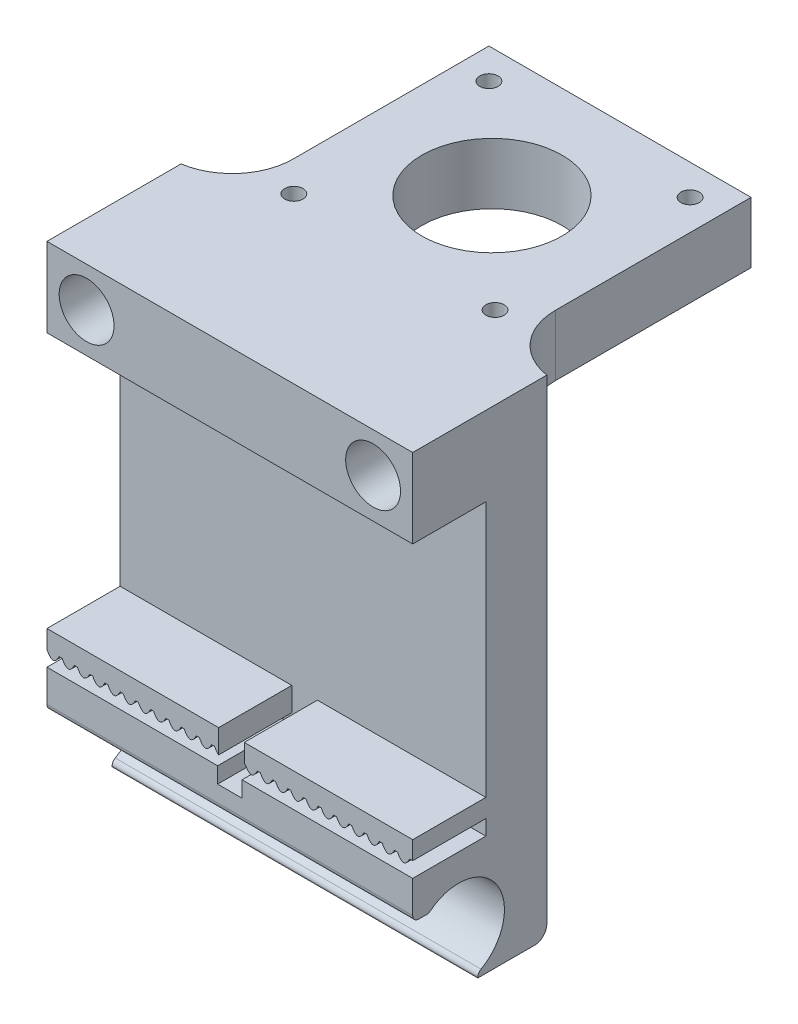
SolidWorks part; units mm, degrees
ref_plane "정면" through (0, 0, 0) normal (0, 0, 1) x (1, 0, 0)
ref_plane "윗면" through (0, 0, 0) normal (0, 1, 0) x (1, 0, 0)
ref_plane "우측면" through (0, 0, 0) normal (1, 0, 0) x (0, 0, -1)
sketch "스케치1" plane through (0, 0, 0) normal (0, 0, 1) x (1, 0, 0)
  line L1 (0, 0) -> (-60, 0)
  line L2 (0, 0) -> (0, 80)
  line L3 (0, 80) -> (-60, 80)
  line L4 (-60, 0) -> (-60, 80)
  dimension "D1" = 60
  dimension "D2" = 80
extrude "보스-돌출1" add sketch "스케치1" along normal blind 10
sketch "스케치2" plane through (0, 0, 10) normal (0, 0, 1) x (1, 0, 0)
  line L0 (0, 0) -> (0, 80) construction
  line L1 (-60, 80) -> (0, 80)
  line L2 (-60, 80) -> (-60, 67)
  line L3 (-60, 67) -> (0, 67)
  line L4 (0, 80) -> (0, 67)
  circle A0 centre (-6.5, 73.5) radius 4
  circle A1 centre (-53.5, 73.5) radius 4
  dimension "D2" = 6.5
  dimension "D3" = 6.5
  dimension "D4" = 6.5
  dimension "D1" = 13
extrude "보스-돌출2" add sketch "스케치2" along normal blind 12
sketch "스케치3" plane through (0, 0, 10) normal (0, 0, 1) x (1, 0, 0)
  line L0 (0, 0) -> (0, 67) construction
  line L1 (-60, 0) -> (0, 0)
  line L2 (-60, 0) -> (-60, 20)
  line L3 (-60, 20) -> (0, 20)
  line L4 (0, 0) -> (0, 20)
  dimension "D1" = 20
extrude "보스-돌출3" add sketch "스케치3" along normal blind 12
sketch "스케치6" plane through (0, 0, 0) normal (1, 0, 0) x (0, 0, -1)
  circle A0 centre (-14.4537, 7.5501) radius 7.5
extrude "컷-돌출1" cut sketch "스케치6" against normal blind 60
sketch "스케치7" plane through (0, 0, 0) normal (1, 0, 0) x (0, 0, -1)
  line L0 (-22, 7.7525) -> (-22, 0)
  line L1 (-22, 0) -> (-22, 20) construction
sketch "스케치8" plane through (0, 0, 0) normal (1, 0, 0) x (0, 0, -1)
  line L0 (-14.2542, 0) -> (-22, 0)
  line L1 (-22, 0) -> (0, 0) construction
  line L2 (-22, 0) -> (-22, 7.7525)
  line L3 (-22, 7.7525) -> (-14.2542, 0)
extrude "컷-돌출3" cut sketch "스케치8" against normal blind 60
sketch "스케치9" plane through (0, 0, 0) normal (1, 0, 0) x (0, 0, -1)
  line L0 (-19.3678, 13.216) -> (-22, 13.216)
  line L1 (-22, 7.7525) -> (-22, 20) construction
  line L2 (-22, 13.216) -> (-22, 7.7525)
  line L3 (-22, 7.7525) -> (-19.3678, 13.216)
  line L5 (-14.2542, 0) -> (0, 0) construction
  line L7 (-11.3118, 0.74) -> (-11.3118, 0)
  line L8 (-11.3118, 0.74) -> (-11.3118, 0.8256)
  line L9 (-11.3118, 0.8256) -> (-14.6498, 0)
  line L10 (-14.6498, 0) -> (-11.3118, 0)
  arc A0 (-14.3058, 0.0516) -> (-21.9521, 7.7046) centre (-14.4537, 7.5501) ccw construction
sketch "스케치10" plane through (0, 0, 0) normal (1, 0, 0) x (0, 0, -1)
  line L0 (-19.3678, 13.216) -> (-22, 13.216)
  line L1 (-22, 13.216) -> (-22, 7.4759)
  line L2 (-22, 7.7525) -> (-22, 0) construction
  line L3 (-22, 7.4759) -> (-19.3678, 13.216)
  line L4 (-11.3118, 0) -> (-15.1355, 0)
  line L5 (-15.1355, 0) -> (-11.3118, 1.4319)
  line L6 (-11.3118, 1.4319) -> (-11.3118, 0)
extrude "컷-돌출6" cut sketch "스케치10" against normal blind 60
fillet "필렛11" radius 1 3 edges at (-30, 13.216, 22) (-30, 13.216, 19.3678) (-30, 0.74, 11.3118)
sketch "스케치11" plane through (0, 0, 10) normal (0, 0, 1) x (1, 0, 0)
  line L0 (-60, 67) -> (-60, 20) construction
  line L1 (-60, 21.5) -> (0, 21.5)
  line L2 (-60, 21.5) -> (-60, 25)
  line L3 (-60, 25) -> (0, 25)
  line L4 (0, 21.5) -> (0, 25)
  line L5 (0, 20) -> (0, 67) construction
  line L6 (0, 20) -> (-60, 20) construction
  dimension "D1" = 1.5
  dimension "D2" = 3.5
extrude "보스-돌출4" add sketch "스케치11" along normal blind 12
sketch "스케치13" plane through (0, 0, 22) normal (0, 0, 1) x (1, 0, 0)
  line L0 (-60, 20) -> (-60, 14.216) construction
  line L1 (-32, 18.3877) -> (-28, 18.3877)
  line L2 (-32, 18.3877) -> (-32, 16.8877)
  line L3 (-32, 16.8877) -> (-28, 16.8877)
  line L4 (-28, 18.3877) -> (-28, 16.8877)
  line L5 (0, 14.216) -> (0, 20) construction
  point P4 (-32, 17.6377)
  dimension "D1" = 28
  dimension "D2" = 28
sketch "스케치14" plane through (0, 0, 22) normal (0, 0, 1) x (1, 0, 0)
  line L0 (-32, 16.8877) -> (-32, 18.3877)
  line L1 (-32, 18.3877) -> (-28, 18.3877)
  line L2 (-28, 18.3877) -> (-28, 16.8877)
  line L3 (-28, 16.8877) -> (-32, 16.8877)
extrude "컷-돌출8" cut sketch "스케치14" against normal blind 22
fillet "필렛12" radius 2 1 edges at (-30, 0, 0)
sketch "스케치15" plane through (-60, 0, 0) normal (-1, 0, 0) x (0, 0, 1)
  line L0 (22, 25) -> (22, 21.5) construction
  line L1 (10, 21.5) -> (22, 21.5)
  line L2 (10, 21.5) -> (10, 22)
  line L3 (10, 22) -> (22, 22)
  line L4 (22, 21.5) -> (22, 22)
  dimension "D1" = 0.5
extrude "컷-돌출9" cut sketch "스케치15" against normal through all
sketch "스케치17" plane through (0, 0, 22) normal (0, 0, 1) x (1, 0, 0)
  line L0 (-60, 20) -> (-60, 21)
  line L1 (-60, 22) -> (-60, 20) construction
  line L2 (-60, 21) -> (-4.2919, 21)
  line L3 (-4.2919, 21) -> (-4.2919, 20)
  line L4 (0, 20) -> (-60, 20) construction
  line L5 (0, 22) -> (-60, 22) construction
  line L6 (-60, 22) -> (-58.0632, 22)
  line L7 (-57.5, 22) -> (-55.5632, 22)
  line L8 (-55, 22) -> (-53.0632, 22)
  line L9 (-52.5, 22) -> (-50.5632, 22)
  line L10 (-50, 22) -> (-48.0632, 22)
  line L11 (-47.5, 22) -> (-45.5632, 22)
  line L12 (-45, 22) -> (-43.0632, 22)
  line L13 (-42.5, 22) -> (-40.5632, 22)
  line L14 (-40, 22) -> (-38.0632, 22)
  line L15 (-37.5, 22) -> (-35.5632, 22)
  line L16 (-35, 22) -> (-33.0632, 22)
  line L17 (-32.5, 22) -> (-30.5632, 22)
  line L18 (-30, 22) -> (-28.0632, 22)
  line L19 (-27.5, 22) -> (-25.5632, 22)
  line L20 (-25, 22) -> (-23.0632, 22)
  line L21 (-22.5, 22) -> (-20.5632, 22)
  line L22 (-20, 22) -> (-18.0632, 22)
  line L23 (-17.5, 22) -> (-15.5632, 22)
  line L24 (-15, 22) -> (-13.0632, 22)
  line L25 (-12.5, 22) -> (-10.5632, 22)
  line L26 (-10, 22) -> (-8.0632, 22)
  line L27 (-7.5, 22) -> (-5.5632, 22)
  line L28 (-5, 22) -> (-3.0632, 22)
  line L29 (-2.5, 22) -> (-0.5632, 22)
  spline S0 degree 2 poles (-60, 22) (-59.0652, 19.9995) (-58.0632, 22) knots 0 0 0 1 1 1
  spline S1 degree 2 poles (-57.5, 22) (-56.5652, 19.9995) (-55.5632, 22) knots 0 0 0 1 1 1
  spline S2 degree 2 poles (-55, 22) (-54.0652, 19.9995) (-53.0632, 22) knots 0 0 0 1 1 1
  spline S3 degree 2 poles (-52.5, 22) (-51.5652, 19.9995) (-50.5632, 22) knots 0 0 0 1 1 1
  spline S4 degree 2 poles (-50, 22) (-49.0652, 19.9995) (-48.0632, 22) knots 0 0 0 1 1 1
  spline S5 degree 2 poles (-47.5, 22) (-46.5652, 19.9995) (-45.5632, 22) knots 0 0 0 1 1 1
  spline S6 degree 2 poles (-45, 22) (-44.0652, 19.9995) (-43.0632, 22) knots 0 0 0 1 1 1
  spline S7 degree 2 poles (-42.5, 22) (-41.5652, 19.9995) (-40.5632, 22) knots 0 0 0 1 1 1
  spline S8 degree 2 poles (-40, 22) (-39.0652, 19.9995) (-38.0632, 22) knots 0 0 0 1 1 1
  spline S9 degree 2 poles (-37.5, 22) (-36.5652, 19.9995) (-35.5632, 22) knots 0 0 0 1 1 1
  spline S10 degree 2 poles (-35, 22) (-34.0652, 19.9995) (-33.0632, 22) knots 0 0 0 1 1 1
  spline S11 degree 2 poles (-32.5, 22) (-31.5652, 19.9995) (-30.5632, 22) knots 0 0 0 1 1 1
  spline S12 degree 2 poles (-30, 22) (-29.0652, 19.9995) (-28.0632, 22) knots 0 0 0 1 1 1
  spline S13 degree 2 poles (-27.5, 22) (-26.5652, 19.9995) (-25.5632, 22) knots 0 0 0 1 1 1
  spline S14 degree 2 poles (-25, 22) (-24.0652, 19.9995) (-23.0632, 22) knots 0 0 0 1 1 1
  spline S15 degree 2 poles (-22.5, 22) (-21.5652, 19.9995) (-20.5632, 22) knots 0 0 0 1 1 1
  spline S16 degree 2 poles (-20, 22) (-19.0652, 19.9995) (-18.0632, 22) knots 0 0 0 1 1 1
  spline S17 degree 2 poles (-17.5, 22) (-16.5652, 19.9995) (-15.5632, 22) knots 0 0 0 1 1 1
  spline S18 degree 2 poles (-15, 22) (-14.0652, 19.9995) (-13.0632, 22) knots 0 0 0 1 1 1
  spline S19 degree 2 poles (-12.5, 22) (-11.5652, 19.9995) (-10.5632, 22) knots 0 0 0 1 1 1
  spline S20 degree 2 poles (-10, 22) (-9.0652, 19.9995) (-8.0632, 22) knots 0 0 0 1 1 1
  spline S21 degree 2 poles (-7.5, 22) (-6.5652, 19.9995) (-5.5632, 22) knots 0 0 0 1 1 1
  spline S22 degree 2 poles (-5, 22) (-4.0652, 19.9995) (-3.0632, 22) knots 0 0 0 1 1 1
  spline S23 degree 2 poles (-2.5, 22) (-1.5652, 19.9995) (-0.5632, 22) knots 0 0 0 1 1 1
  dimension "D1" = 24
sketch "스케치18" plane through (0, 0, 22) normal (0, 0, 1) x (1, 0, 0)
  line L0 (0, 22) -> (-60, 22) construction
  line L1 (-60, 22) -> (-58, 22)
  line L2 (-57.5, 22) -> (-55.5, 22)
  line L3 (-55, 22) -> (-53, 22)
  line L4 (-52.5, 22) -> (-50.5, 22)
  line L5 (-50, 22) -> (-48, 22)
  line L6 (-47.5, 22) -> (-45.5, 22)
  line L7 (-45, 22) -> (-43, 22)
  line L8 (-42.5, 22) -> (-40.5, 22)
  line L9 (-40, 22) -> (-38, 22)
  line L10 (-37.5, 22) -> (-35.5, 22)
  line L11 (-35, 22) -> (-33, 22)
  line L12 (-32.5, 22) -> (-30.5, 22)
  line L13 (-30, 22) -> (-28, 22)
  line L14 (-27.5, 22) -> (-25.5, 22)
  line L15 (-25, 22) -> (-23, 22)
  line L16 (-22.5, 22) -> (-20.5, 22)
  line L17 (-20, 22) -> (-18, 22)
  line L18 (-17.5, 22) -> (-15.5, 22)
  line L19 (-15, 22) -> (-13, 22)
  line L20 (-12.5, 22) -> (-10.5, 22)
  line L21 (-10, 22) -> (-8, 22)
  line L22 (-7.5, 22) -> (-5.5, 22)
  line L23 (-5, 22) -> (-3, 22)
  line L24 (-2.5, 22) -> (-0.5, 22)
  spline S0 degree 2 poles (-60, 22) (-59, 20) (-58, 22) knots 0 0 0 1 1 1
  spline S1 degree 2 poles (-57.5, 22) (-56.5, 20) (-55.5, 22) knots 0 0 0 1 1 1
  spline S2 degree 2 poles (-55, 22) (-54, 20) (-53, 22) knots 0 0 0 1 1 1
  spline S3 degree 2 poles (-52.5, 22) (-51.5, 20) (-50.5, 22) knots 0 0 0 1 1 1
  spline S4 degree 2 poles (-50, 22) (-49, 20) (-48, 22) knots 0 0 0 1 1 1
  spline S5 degree 2 poles (-47.5, 22) (-46.5, 20) (-45.5, 22) knots 0 0 0 1 1 1
  spline S6 degree 2 poles (-45, 22) (-44, 20) (-43, 22) knots 0 0 0 1 1 1
  spline S7 degree 2 poles (-42.5, 22) (-41.5, 20) (-40.5, 22) knots 0 0 0 1 1 1
  spline S8 degree 2 poles (-40, 22) (-39, 20) (-38, 22) knots 0 0 0 1 1 1
  spline S9 degree 2 poles (-37.5, 22) (-36.5, 20) (-35.5, 22) knots 0 0 0 1 1 1
  spline S10 degree 2 poles (-35, 22) (-34, 20) (-33, 22) knots 0 0 0 1 1 1
  spline S11 degree 2 poles (-32.5, 22) (-31.5, 20) (-30.5, 22) knots 0 0 0 1 1 1
  spline S12 degree 2 poles (-30, 22) (-29, 20) (-28, 22) knots 0 0 0 1 1 1
  spline S13 degree 2 poles (-27.5, 22) (-26.5, 20) (-25.5, 22) knots 0 0 0 1 1 1
  spline S14 degree 2 poles (-25, 22) (-24, 20) (-23, 22) knots 0 0 0 1 1 1
  spline S15 degree 2 poles (-22.5, 22) (-21.5, 20) (-20.5, 22) knots 0 0 0 1 1 1
  spline S16 degree 2 poles (-20, 22) (-19, 20) (-18, 22) knots 0 0 0 1 1 1
  spline S17 degree 2 poles (-17.5, 22) (-16.5, 20) (-15.5, 22) knots 0 0 0 1 1 1
  spline S18 degree 2 poles (-15, 22) (-14, 20) (-13, 22) knots 0 0 0 1 1 1
  spline S19 degree 2 poles (-12.5, 22) (-11.5, 20) (-10.5, 22) knots 0 0 0 1 1 1
  spline S20 degree 2 poles (-10, 22) (-9, 20) (-8, 22) knots 0 0 0 1 1 1
  spline S21 degree 2 poles (-7.5, 22) (-6.5, 20) (-5.5, 22) knots 0 0 0 1 1 1
  spline S22 degree 2 poles (-5, 22) (-4, 20) (-3, 22) knots 0 0 0 1 1 1
  spline S23 degree 2 poles (-2.5, 22) (-1.5, 20) (-0.5, 22) knots 0 0 0 1 1 1
  dimension "D1" = 24
extrude "보스-돌출5" add sketch "스케치18" against normal blind 20
sketch "스케치19" plane through (0, 0, 22) normal (0, 0, 1) x (1, 0, 0)
  line L0 (0, 14.216) -> (0, 20) construction
  line L1 (-60, 20) -> (0, 20)
  line L2 (-60, 20) -> (-60, 19.5)
  line L3 (-60, 19.5) -> (0, 19.5)
  line L4 (0, 20) -> (0, 19.5)
  line L5 (0, 25) -> (-60, 25) construction
  line L6 (-31.8375, 25) -> (-27.6347, 25)
  line L7 (-31.8375, 25) -> (-31.8375, 21)
  line L8 (-31.8375, 21) -> (-27.6347, 21)
  line L9 (-27.6347, 25) -> (-27.6347, 21)
  dimension "D1" = 0.5
extrude "컷-돌출10" cut sketch "스케치19" against normal blind 12
sketch "스케치20" plane through (0, 0, 22) normal (0, 0, 1) x (1, 0, 0)
  line L0 (-60, 19.5) -> (0, 19.5) construction
  line L1 (-32, 18.3877) -> (-28, 18.3877)
  line L2 (-32, 18.3877) -> (-32, 19.5)
  line L3 (-32, 19.5) -> (-28, 19.5)
  line L4 (-28, 18.3877) -> (-28, 19.5)
  dimension "D1" = 4
sketch "스케치21" plane through (0, 0, 22) normal (0, 0, 1) x (1, 0, 0)
  line L1 (-32, 19.5) -> (-28, 19.5)
  line L2 (-32, 19.5) -> (-32, 18.3877)
  line L3 (-32, 18.3877) -> (-28, 18.3877)
  line L4 (-28, 19.5) -> (-28, 18.3877)
extrude "컷-돌출12" cut sketch "스케치21" against normal through all
sketch "스케치22" plane through (0, 0, 22) normal (0, 0, 1) x (1, 0, 0)
  circle A0 centre (-53.5, 73.5) radius 4.5
  circle A1 centre (-6.5, 73.5) radius 4.5
extrude "컷-돌출14" cut sketch "스케치22" against normal blind 12
sketch "스케치23" plane through (0, 80, 0) normal (0, 1, 0) x (1, 0, 0)
  line L0 (0, 0) -> (-60, 0)
  line L1 (-30, 0) -> (-51.5006, 0)
  line L2 (-30, 0) -> (-8.4994, 0)
  line L3 (-30, 0) -> (-30, 42)
  line L4 (-8.4994, 0) -> (-51.5006, 0)
  line L5 (-8.4994, 0) -> (-8.4994, 42)
  line L6 (-8.4994, 42) -> (-51.5006, 42)
  line L7 (-51.5006, 0) -> (-51.5006, 42)
  line L9 (-51.5006, 0) -> (-46.5006, 0)
  line L10 (-51.5006, 0) -> (-51.5006, 5)
  line L11 (-51.5006, 5) -> (-46.5006, 5)
  line L12 (-46.5006, 0) -> (-46.5006, 5)
  circle A0 centre (-30, 21) radius 11.5
  circle A1 centre (-46.5006, 5) radius 1.5
  circle A2 centre (-13.4994, 5) radius 1.5
  circle A3 centre (-13.4994, 37) radius 1.5
  circle A4 centre (-46.5006, 37) radius 1.5
  dimension "D2" = 5
  dimension "D4" = 5
  dimension "D5" = 5
  dimension "D1" = 42
  dimension "D3" = 5
extrude "보스-돌출6" add sketch "스케치23" against normal blind 10 contours A0 L3 L0 L5 L6 A3 A2 | A1 L12 L0 L3 A0 L6 L7 L11 A4 | A1 L11 L7 L4 L12 region at (-17.5789, 80, -21) region at (-42.1837, 80, -21.6583) region at (-49.1423, 80, -2.3583)
fillet "필렛13" radius 10 2 edges at (-8.4994, 75, 0) (-51.5006, 75, 0)
